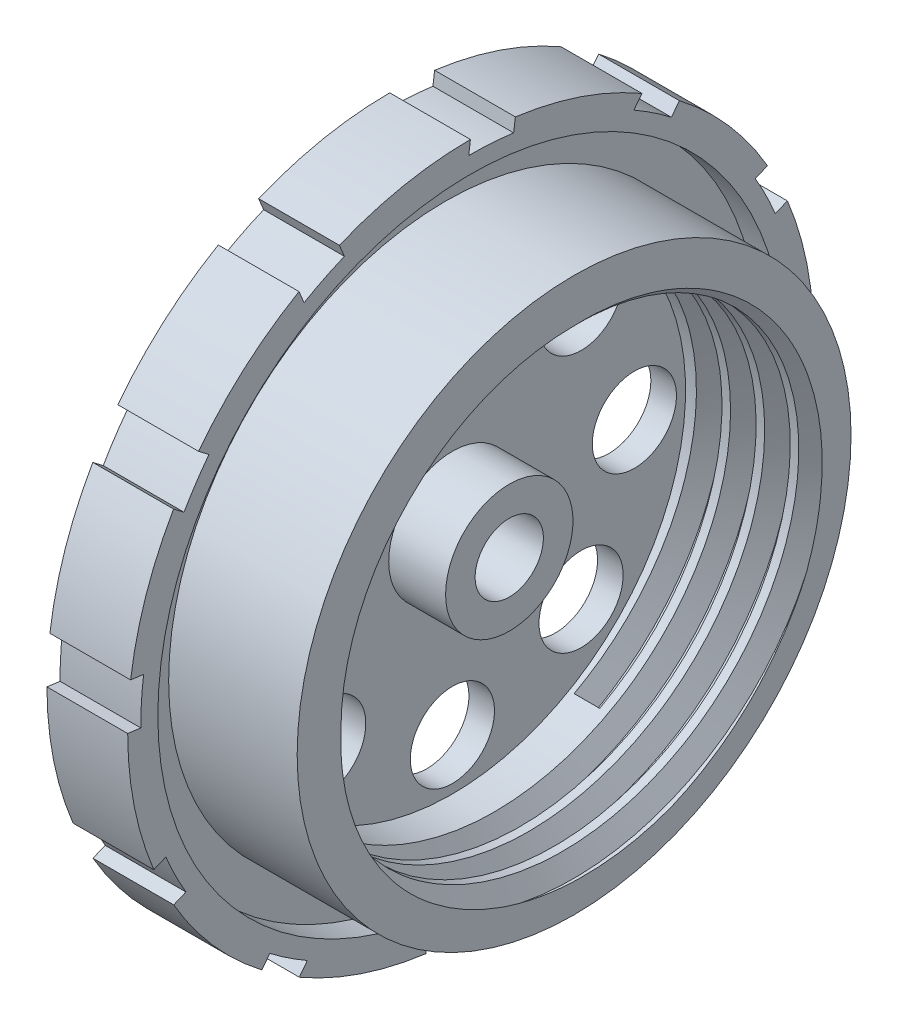
SolidWorks part; units mm, degrees
ref_plane "Front" through (0, 0, 0) normal (0, 0, 1) x (1, 0, 0)
ref_plane "Top" through (0, 0, 0) normal (0, 1, 0) x (1, 0, 0)
ref_plane "Right" through (0, 0, 0) normal (1, 0, 0) x (0, 0, -1)
sketch "Sketch1" plane through (0, 0, 0) normal (0, 0, 1) x (1, 0, 0)
  line L2 (3.25, 0) -> (3.25, 26.75)
  line L3 (3.25, 26.75) -> (0, 26.75)
  line L4 (0, 26.75) -> (0, 30.15)
  line L5 (0, 30.15) -> (7.1, 30.15)
  line L6 (7.1, 30.15) -> (7.1, 27.5)
  line L7 (7.1, 27.5) -> (4.9, 27.5)
  line L8 (4.9, 27.5) -> (4.9, 24.35)
  line L9 (4.9, 24.35) -> (16.2, 24.35)
  line L10 (16.2, 24.35) -> (16.2, 20.5)
  line L11 (16.2, 20.5) -> (5.5, 20.5)
  line L12 (5.5, 20.5) -> (5.5, 5.6)
  line L13 (5.5, 5.6) -> (10.5, 5.6)
  line L14 (10.5, 5.6) -> (10.5, 0)
  line L17 (10.5, 0) -> (3.25, 0)
  line L18 (0, 0) -> (29.6651, 0) construction
  dimension "D1" = 60.3
  dimension "D2" = 53.5
  dimension "D3" = 3.25
  dimension "D4" = 7.1
  dimension "D5" = 55
  dimension "D6" = 48.7
  dimension "D7" = 2.2
  dimension "D8" = 16.2
  dimension "D9" = 41
  dimension "D10" = 10.7
  dimension "D11" = 5
  dimension "D12" = 11.2
revolve "Revolve1" add sketch "Sketch1" angle 360 about L18
sketch "Sketch2" plane through (10.5, 0, 0) normal (1, 0, 0) x (0, 0, -1)
  circle A0 centre (0, 0) radius 3
  dimension "D1" = 6
extrude "Cut-Extrude1" cut sketch "Sketch2" against normal through all
sketch "Sketch3" plane through (3.25, 0, 0) normal (-1, 0, 0) x (0, 0, 1)
  circle A0 centre (16, 0) radius 3.7
  dimension "D1" = 7.4
  dimension "D2" = 16
extrude "Cut-Extrude2" cut sketch "Sketch3" against normal blind 10
pattern_circular "CirPattern1" count 8 over 360 about axis through (0, 0, 0) along (1, 0, 0) of "Cut-Extrude2"
sketch "Sketch4" plane through (0, 0, 0) normal (-1, 0, 0) x (0, 0, 1)
  line L0 (16, 0) -> (11.3137, -11.3137)
  line L1 (26.7925, -11.0978) -> (27.855, -11.5379)
  line L2 (25.0312, -14.6437) -> (26.1033, -15.0878)
  line L3 (12.1453, -9.3062) -> (32.7219, -17.8293) construction
  line L4 (13.6569, -5.6569) -> (34.2335, -14.18) construction
  arc A0 (25.0312, -14.6437) -> (26.7925, -11.0978) centre (0, 0) ccw
  arc A1 (26.1033, -15.0878) -> (27.855, -11.5379) centre (0, 0) ccw
  dimension "D2" = 58
  dimension "D1" = 3.95
extrude "Cut-Extrude3" cut sketch "Sketch4" against normal through all contours A1 L1 A0 L2
pattern_circular "CirPattern2" count 12 over 360 about axis through (0, 0, 0) along (1, 0, 0) of "Cut-Extrude3" reverse direction yes
thread "Thread1" pitch 3 method cut profile "Thread Profile1" start angle 0, offset 3, length 11, pitch 3, diameter 41
ref_plane "Plane1" through (19.2, 0, 20.5) normal (0, -1, 0) x (0, 0, 1)
sketch "Thread Profile1" plane through (19.2, 0, 20.5) normal (0, -1, 0) x (0, 0, 1)
  line L0 (0, 0) -> (0, 3) construction
  line L1 (0, 0) -> (1.6238, 0.9375)
  line L2 (1.6238, 0.9375) -> (1.6238, 1.3125)
  line L3 (1.6238, 1.3125) -> (0, 2.25)
  line L4 (1.6238, 1.125) -> (0, 1.125) construction
  line L11 (0, 0) -> (0, 2.25)
  point P2 (0, 0)
  dimension "Pitch" = 3
  dimension "Profile_Angle" = 60
  dimension "Profile_Land" = 0.375
  dimension "Profile_Height" = 1.6238
